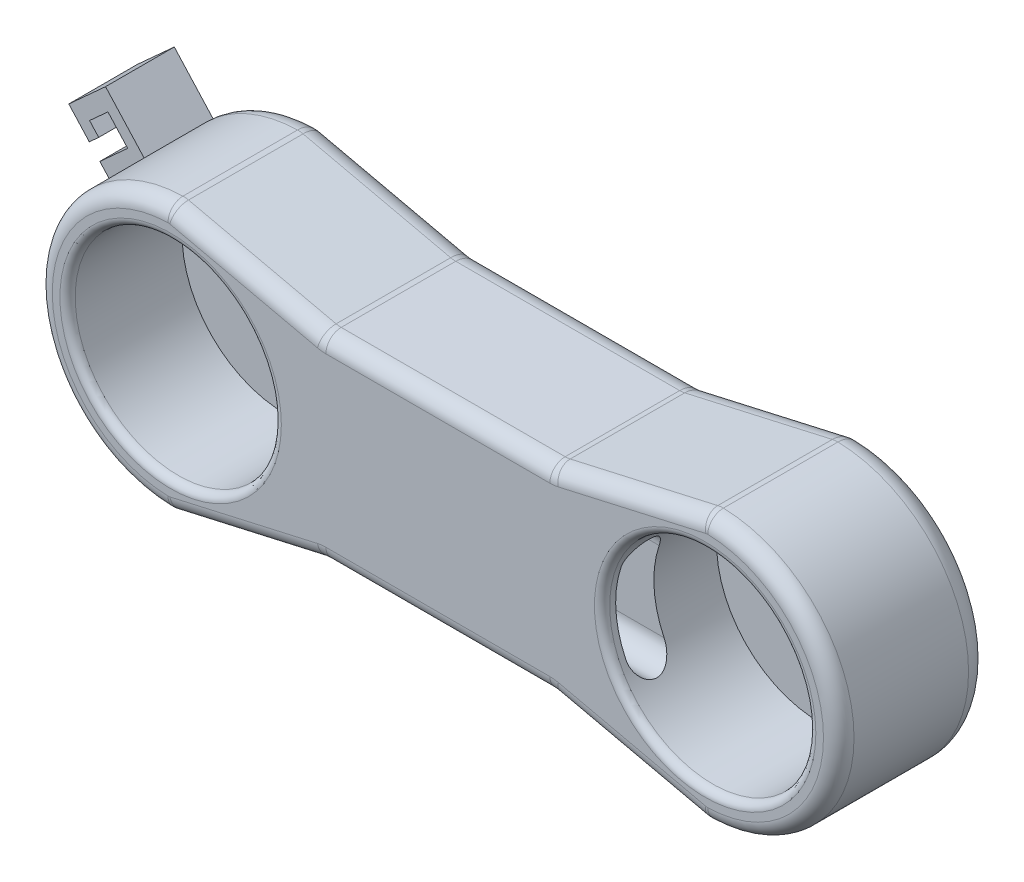
SolidWorks part; units mm, degrees
material "ABS"
ref_plane "Front Plane" through (0, 0, 0) normal (0, 0, 1) x (1, 0, 0)
ref_plane "Top Plane" through (0, 0, 0) normal (0, 1, 0) x (1, 0, 0)
ref_plane "Right Plane" through (0, 0, 0) normal (1, 0, 0) x (0, 0, -1)
sketch "Sketch10" plane through (0, 0, 0) normal (0, 0, 1) x (1, 0, 0)
  line L0 (-68.2242, 0) -> (70, 0) construction
  line L1 (0, 17.5) -> (20, 12.9672)
  line L2 (20, 12.9672) -> (50, 12.9672)
  line L3 (50, 12.9672) -> (70, 17.5)
  line L4 (50, -12.9672) -> (70, -17.5)
  line L5 (20, -12.9672) -> (50, -12.9672)
  line L6 (0, -17.5) -> (20, -12.9672)
  circle A1 centre (0, 0) radius 17.5
  circle A2 centre (70, 0) radius 17.5
  point P14 (-17.5, 0)
  point P15 (87.5, 0)
  dimension "D1" = 35
  dimension "D2" = 35
  dimension "D3" = 30
  dimension "D4" = 20
  dimension "D5" = 20
extrude "Boss-Extrude2" add sketch "Sketch10" along normal blind 20 contours A1 L0 L1 | L0 A1 L6 | A1 L0 A2 L3 L2 L1 | L0 A1 L6 L5 L4 A2 | L3 A2 L4 region at (-0.0178, 7.3834, 0) region at (-0.0178, -7.3834, 0) region at (35, 7.0913, 0) region at (35, -7.0913, 0) region at (70.0178, 0, 0)
sketch "Sketch12" plane through (0, 0, 20) normal (0, 0, 1) x (1, 0, 0)
  circle A0 centre (0, 0) radius 13.5
  circle A1 centre (70, 0) radius 13.5
  dimension "D1" = 27
  dimension "D2" = 27
extrude "Cut-Extrude3" cut sketch "Sketch12" against normal blind 15
sketch "Sketch13" plane through (0, 0, 5) normal (0, 0, 1) x (1, 0, 0)
  line L0 (0, 8.9878) -> (0, -6.869) construction
  circle A0 centre (0, 0) radius 0.889
  circle A1 centre (-8.306, 0) radius 0.5335
  circle A3 centre (8.306, 0) radius 0.5335
  dimension "D1" = 1.778
  dimension "D2" = 1.067
  dimension "D4" = 8.306
extrude "Cut-Extrude4" cut sketch "Sketch13" against normal through all
sketch "Sketch14" plane through (0, 0, 5) normal (0, 0, 1) x (1, 0, 0)
  line L0 (70, 10.1142) -> (70, -9.7577) construction
  circle A0 centre (70, 0) radius 0.889
  circle A1 centre (78.306, 0) radius 0.5335
  circle A2 centre (61.694, 0) radius 0.5335
  dimension "D1" = 1.778
  dimension "D2" = 1.067
  dimension "D3" = 16.612
extrude "Cut-Extrude5" cut sketch "Sketch14" against normal through all
fillet "Fillet2" radius 3 8 edges at (70, -17.5, 10) (50, -12.9672, 10) (20, -12.9672, 10) (0, -17.5, 10) (70, 17.5, 10) (50, 12.9672, 10) (20, 12.9672, 10) (0, 17.5, 10)
ref_plane "Plane2" through (10, 0, 0) normal (1, 0, 0) x (0, 0, -1)
sketch "Sketch17" plane through (10, 0, 0) normal (1, 0, 0) x (0, 0, -1)
  line L0 (-15.7192, -5.8668) -> (-15.7192, 4.2724) construction
  line L1 (-18.2192, -5.8668) -> (-18.2192, 4.2724)
  line L2 (-13.2192, -5.8668) -> (-13.2192, 4.2724)
  arc A0 (-18.2192, -5.8668) -> (-13.2192, -5.8668) centre (-15.7192, -5.8668) ccw
  arc A1 (-13.2192, 4.2724) -> (-18.2192, 4.2724) centre (-15.7192, 4.2724) ccw
  point P2 (-15.7192, -0.7972)
  dimension "D1" = 5
extrude "Cut-Extrude8" cut sketch "Sketch17" along normal blind 63
fillet "Fillet3" radius 1 2 edges at (83.5, 0, 20) (13.5, 0, 20)
ref_plane "Plane4" through (-11.762, 12.9579, 0) normal (-0.6721, 0.7404, 0) x (0, 0, -1)
sketch "Sketch19" plane through (-11.762, 12.9579, 0) normal (-0.6721, 0.7404, 0) x (0, 0, -1)
  line L0 (-2.1446, 0.7764) -> (-11.1467, 0.7764)
  line L1 (-2.1446, 0.7764) -> (-2.1446, 7.2773)
  line L2 (-11.1467, 0.7764) -> (-11.1467, 7.2773)
  line L3 (-2.1446, 7.2773) -> (-11.1467, 7.2773)
extrude "Boss-Extrude3" add sketch "Sketch19" against normal up to surface and the other way blind 7.5 up to face at (-8.9432, 0, 10)
sketch "Sketch21" plane through (0, 0, 11.1467) normal (0, 0, 1) x (1, 0, 0)
  line L8 (-19.5088, 10.6648) -> (-18.2752, 11.7844)
  line L9 (-22.1913, 13.6201) -> (-16.0852, 6.8932) construction
  line L10 (-18.2752, 11.7844) -> (-19.471, 13.1018)
  line L11 (-19.471, 13.1018) -> (-17.0628, 15.2877)
  line L12 (-17.0628, 15.2877) -> (-14.4808, 12.4431)
  line L13 (-14.4808, 12.4431) -> (-18.1224, 9.1375)
  line L14 (-18.1224, 9.1375) -> (-19.5088, 10.6648)
extrude "Cut-Extrude9" cut sketch "Sketch21" against normal through all both and the other way through all
fillet "Fillet9" radius 2 16 edges at (-0.0194, -17.4814, 20) (10.0078, -15.2319, 20) (20.0021, -12.9859, 20) (70.0194, -17.4814, 20) (59.9922, -15.2319, 20) (49.9979, -12.9859, 20) (-0.0194, 17.4814, 20) (10.0078, 15.2319, 20) (20.0021, 12.9859, 20) (70.0194, 17.4814, 20) (59.9922, 15.2319, 20) (49.9979, 12.9859, 20) (35, -12.9672, 20) (35, 12.9672, 20) (-17.5, 0, 20) (87.5, 0, 20)
fillet "Fillet11" radius 3 16 edges at (20.0021, 12.9859, 0) (10.0078, 15.2319, 0) (-0.0194, 17.4814, 0) (-17.5, 0, 0) (-0.0194, -17.4814, 0) (10.0078, -15.2319, 0) (20.0021, -12.9859, 0) (35, -12.9672, 0) (49.9979, -12.9859, 0) (59.9922, -15.2319, 0) (70.0194, -17.4814, 0) (87.5, 0, 0) (70.0194, 17.4814, 0) (59.9922, 15.2319, 0) (49.9979, 12.9859, 0) (35, 12.9672, 0)
